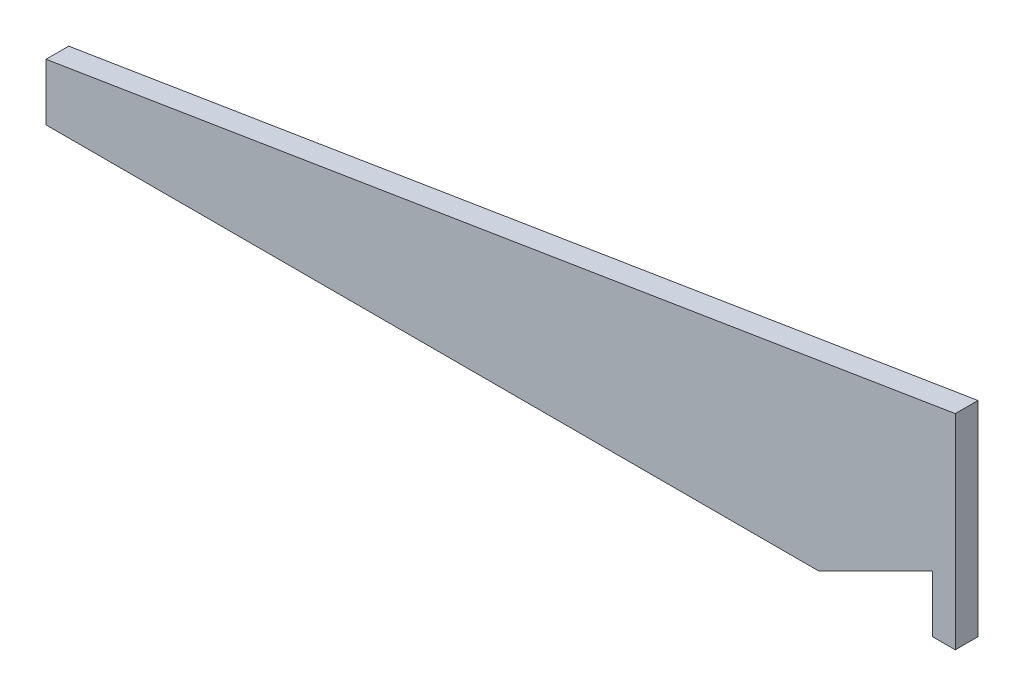
SolidWorks part; units mm, degrees
ref_plane "Front Plane" through (0, 0, 0) normal (0, 0, 1) x (1, 0, 0)
ref_plane "Top Plane" through (0, 0, 0) normal (0, 1, 0) x (1, 0, 0)
ref_plane "Right Plane" through (0, 0, 0) normal (1, 0, 0) x (0, 0, -1)
sketch "Sketch1" plane through (0, 0, 0) normal (0, 0, 1) x (1, 0, 0)
  line L0 (-31.5105, 0) -> (48.4895, 0)
  line L1 (-31.5105, 0) -> (-31.5105, 5)
  line L2 (-31.5105, 5) -> (48.4895, 18)
  line L3 (48.4895, 18) -> (48.4895, 0)
  line L4 (36.4895, 0) -> (46.4895, 5)
  line L5 (46.4895, 5) -> (46.4895, 0)
  dimension "D1" = 80
  dimension "D2" = 5
  dimension "D3" = 18
  dimension "D4" = 5
  dimension "D5" = 2
  dimension "D6" = 10
extrude "Boss-Extrude1" add sketch "Sketch1" along normal blind 2 contours L4 L5 L0 L3 L2 L1 region at (15.2679, 6.4935, 0)
